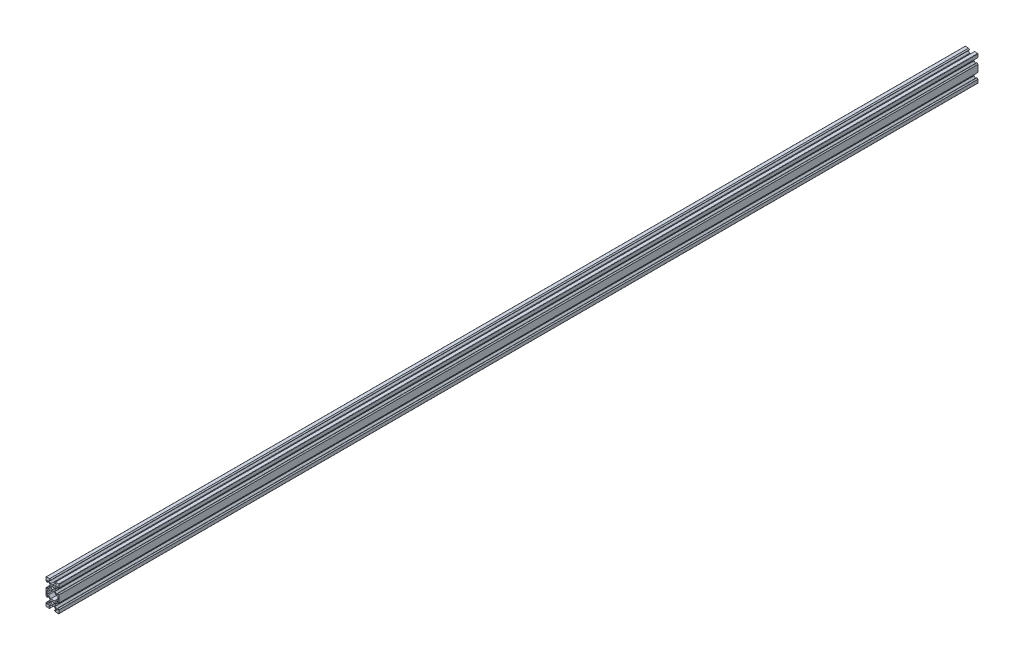
SolidWorks part; units mm, degrees
material "6061-T6 (SS)"
ref_plane "Front Plane" through (0, 0, 0) normal (0, 0, 1) x (1, 0, 0)
ref_plane "Top Plane" through (0, 0, 0) normal (0, 1, 0) x (1, 0, 0)
ref_plane "Right Plane" through (0, 0, 0) normal (1, 0, 0) x (0, 0, -1)
sketch "Sketch1" plane through (0, 0, 0) normal (0, 0, 1) x (1, 0, 0)
  line L0 (0, 0) -> (10, 0) construction
  line L1 (9.5, -20) -> (-9.5, -20)
  line L2 (10, -19.5) -> (10, 19.5)
  line L3 (9.5, 20) -> (-9.5, 20)
  line L4 (-10, -19.5) -> (-10, 19.5)
  line L5 (10, -20) -> (-10, 20) construction
  line L6 (10, 20) -> (-10, -20) construction
  circle A0 centre (0, 10) radius 2.1
  circle A1 centre (0, -10) radius 2.1
  arc A2 (-9.5, -20) -> (-10, -19.5) centre (-9.5, -19.5) cw
  arc A3 (9.5, -20) -> (10, -19.5) centre (9.5, -19.5) ccw
  arc A4 (10, 19.5) -> (9.5, 20) centre (9.5, 19.5) ccw
  arc A5 (-9.5, 20) -> (-10, 19.5) centre (-9.5, 19.5) ccw
  point P0 (0, 0)
  line B0 (0, 10) -> (0, 20) construction
  line B1 (0, 13.69) -> (-0.21, 13.9)
  line B2 (-0.21, 13.9) -> (-2.8393, 13.9)
  line B3 (-2.8393, 13.9) -> (-5.5, 16.5607)
  line B4 (-5.5, 16.5607) -> (-5.5, 18.2)
  line B5 (-5.5, 18.2) -> (-3.125, 18.2)
  line B6 (-3.125, 18.2) -> (-3.125, 18.545)
  line B7 (-3.125, 18.545) -> (-4.58, 20)
  line B8 (-4.58, 20) -> (4.58, 20)
  line B9 (0, 10) -> (-5.9132, 15.9132) construction
  line B10 (3.125, 18.545) -> (4.58, 20)
  line B11 (3.125, 18.2) -> (3.125, 18.545)
  line B12 (5.5, 18.2) -> (3.125, 18.2)
  line B13 (5.5, 16.5607) -> (5.5, 18.2)
  line B14 (2.8393, 13.9) -> (5.5, 16.5607)
  line B15 (0.21, 13.9) -> (2.8393, 13.9)
  line B16 (0, 13.69) -> (0.21, 13.9)
  line B17 (0, 10) -> (-10, 10) construction
  line B18 (-3.69, 10) -> (-3.9, 9.79)
  line B19 (-3.9, 9.79) -> (-3.9, 7.1607)
  line B20 (-3.9, 7.1607) -> (-6.5607, 4.5)
  line B21 (-6.5607, 4.5) -> (-8.2, 4.5)
  line B22 (-8.2, 4.5) -> (-8.2, 6.875)
  line B23 (-8.2, 6.875) -> (-8.545, 6.875)
  line B24 (-8.545, 6.875) -> (-10, 5.42)
  line B25 (-10, 5.42) -> (-10, 14.58)
  line B26 (0, 10) -> (-5.9132, 4.0868) construction
  line B27 (-8.545, 13.125) -> (-10, 14.58)
  line B28 (-8.2, 13.125) -> (-8.545, 13.125)
  line B29 (-8.2, 15.5) -> (-8.2, 13.125)
  line B30 (-6.5607, 15.5) -> (-8.2, 15.5)
  line B31 (-3.9, 12.8393) -> (-6.5607, 15.5)
  line B32 (-3.9, 10.21) -> (-3.9, 12.8393)
  line B33 (-3.69, 10) -> (-3.9, 10.21)
  line B34 (0, -10) -> (-10, -10) construction
  line B35 (-3.69, -10) -> (-3.9, -10.21)
  line B36 (-3.9, -10.21) -> (-3.9, -12.8393)
  line B37 (-3.9, -12.8393) -> (-6.5607, -15.5)
  line B38 (-6.5607, -15.5) -> (-8.2, -15.5)
  line B39 (-8.2, -15.5) -> (-8.2, -13.125)
  line B40 (-8.2, -13.125) -> (-8.545, -13.125)
  line B41 (-8.545, -13.125) -> (-10, -14.58)
  line B42 (-10, -14.58) -> (-10, -5.42)
  line B43 (0, -10) -> (-5.9132, -15.9132) construction
  line B44 (-8.545, -6.875) -> (-10, -5.42)
  line B45 (-8.2, -6.875) -> (-8.545, -6.875)
  line B46 (-8.2, -4.5) -> (-8.2, -6.875)
  line B47 (-6.5607, -4.5) -> (-8.2, -4.5)
  line B48 (-3.9, -7.1607) -> (-6.5607, -4.5)
  line B49 (-3.9, -9.79) -> (-3.9, -7.1607)
  line B50 (-3.69, -10) -> (-3.9, -9.79)
  line B51 (0, -10) -> (0, -20) construction
  line B52 (0, -13.69) -> (0.21, -13.9)
  line B53 (0.21, -13.9) -> (2.8393, -13.9)
  line B54 (2.8393, -13.9) -> (5.5, -16.5607)
  line B55 (5.5, -16.5607) -> (5.5, -18.2)
  line B56 (5.5, -18.2) -> (3.125, -18.2)
  line B57 (3.125, -18.2) -> (3.125, -18.545)
  line B58 (3.125, -18.545) -> (4.58, -20)
  line B59 (4.58, -20) -> (-4.58, -20)
  line B60 (0, -10) -> (5.9132, -15.9132) construction
  line B61 (-3.125, -18.545) -> (-4.58, -20)
  line B62 (-3.125, -18.2) -> (-3.125, -18.545)
  line B63 (-5.5, -18.2) -> (-3.125, -18.2)
  line B64 (-5.5, -16.5607) -> (-5.5, -18.2)
  line B65 (-2.8393, -13.9) -> (-5.5, -16.5607)
  line B66 (-0.21, -13.9) -> (-2.8393, -13.9)
  line B67 (0, -13.69) -> (-0.21, -13.9)
  line B68 (0, -10) -> (10, -10) construction
  line B69 (3.69, -10) -> (3.9, -9.79)
  line B70 (3.9, -9.79) -> (3.9, -7.1607)
  line B71 (3.9, -7.1607) -> (6.5607, -4.5)
  line B72 (6.5607, -4.5) -> (8.2, -4.5)
  line B73 (8.2, -4.5) -> (8.2, -6.875)
  line B74 (8.2, -6.875) -> (8.545, -6.875)
  line B75 (8.545, -6.875) -> (10, -5.42)
  line B76 (10, -5.42) -> (10, -14.58)
  line B77 (0, -10) -> (5.9132, -4.0868) construction
  line B78 (8.545, -13.125) -> (10, -14.58)
  line B79 (8.2, -13.125) -> (8.545, -13.125)
  line B80 (8.2, -15.5) -> (8.2, -13.125)
  line B81 (6.5607, -15.5) -> (8.2, -15.5)
  line B82 (3.9, -12.8393) -> (6.5607, -15.5)
  line B83 (3.9, -10.21) -> (3.9, -12.8393)
  line B84 (3.69, -10) -> (3.9, -10.21)
  line B85 (0, 10) -> (10, 10) construction
  line B86 (3.69, 10) -> (3.9, 10.21)
  line B87 (3.9, 10.21) -> (3.9, 12.8393)
  line B88 (3.9, 12.8393) -> (6.5607, 15.5)
  line B89 (6.5607, 15.5) -> (8.2, 15.5)
  line B90 (8.2, 15.5) -> (8.2, 13.125)
  line B91 (8.2, 13.125) -> (8.545, 13.125)
  line B92 (8.545, 13.125) -> (10, 14.58)
  line B93 (10, 14.58) -> (10, 5.42)
  line B94 (0, 10) -> (5.9132, 15.9132) construction
  line B95 (8.545, 6.875) -> (10, 5.42)
  line B96 (8.2, 6.875) -> (8.545, 6.875)
  line B97 (8.2, 4.5) -> (8.2, 6.875)
  line B98 (6.5607, 4.5) -> (8.2, 4.5)
  line B99 (3.9, 7.1607) -> (6.5607, 4.5)
  line B100 (3.9, 9.79) -> (3.9, 7.1607)
  line B101 (3.69, 10) -> (3.9, 9.79)
  line B102 (-8.2, -2.7) -> (-8.2, 2.7)
  line B103 (-8.2, 2.7) -> (-6.2393, 2.7)
  line B104 (-6.2393, 2.7) -> (-2.8393, 6.1)
  line B105 (-2.8393, 6.1) -> (2.8393, 6.1)
  line B106 (0, 6.1) -> (0, 0) construction
  line B107 (0, 0) -> (-8.2, 0) construction
  line B108 (6.2393, 2.7) -> (2.8393, 6.1)
  line B109 (8.2, 2.7) -> (6.2393, 2.7)
  line B110 (8.2, -2.7) -> (8.2, 2.7)
  line B111 (8.2, -2.7) -> (6.2393, -2.7)
  line B112 (6.2393, -2.7) -> (2.8393, -6.1)
  line B113 (-2.8393, -6.1) -> (2.8393, -6.1)
  line B114 (-6.2393, -2.7) -> (-2.8393, -6.1)
  line B115 (-8.2, -2.7) -> (-6.2393, -2.7)
  line B116 (0, 6.1) -> (0, 10) construction
  line B117 (0, 10) -> (-5.0927, 4.9073) construction
  dimension "D4" = 4.2
  dimension "D5" = 0.5
  dimension "D1" = 20
  dimension "D2" = 40
  dimension "D3" = 20
sketch_block_instance "V Slot 1-4"
sketch_block "V Slot 1" parameters "D1"=10, "D2"=11, "D3"=4.3, "D4"=1.8, "D5"=0.21, "D6"=45, "D7"=9.16, "D8"=1.5, "D9"=6.25
sketch_block_instance "V Slot 1-5"
sketch_block_instance "V Slot 1-6"
sketch_block_instance "V Slot 1-7"
sketch_block_instance "V Slot 1-8"
sketch_block_instance "V Slot 1-9"
sketch_block_instance "Center Cutout 1-1"
sketch_block "Center Cutout 1" parameters "D1"=5.4, "D2"=12.2, "D3"=8.2, "D4"=45, "D5"=10, "D6"=1.5
extrude "Boss-Extrude1" add sketch "Sketch1" along normal blind 1422.4 contours B101 B86 B87 B88 B89 B90 B91 B92 L2 A4 L3 B10 B11 B12 B13 B14 B15 B16 B1 B2 B3 B4 B5 B6 B7 A5 L4 B27 B28 B29 B30 B31 B32 B33 B18 B19 B20 B21 B22 B23 B24 B44 B45 B46 B47 B48 B49 B50 B35 region at (7.04, -19.5528, 0)
